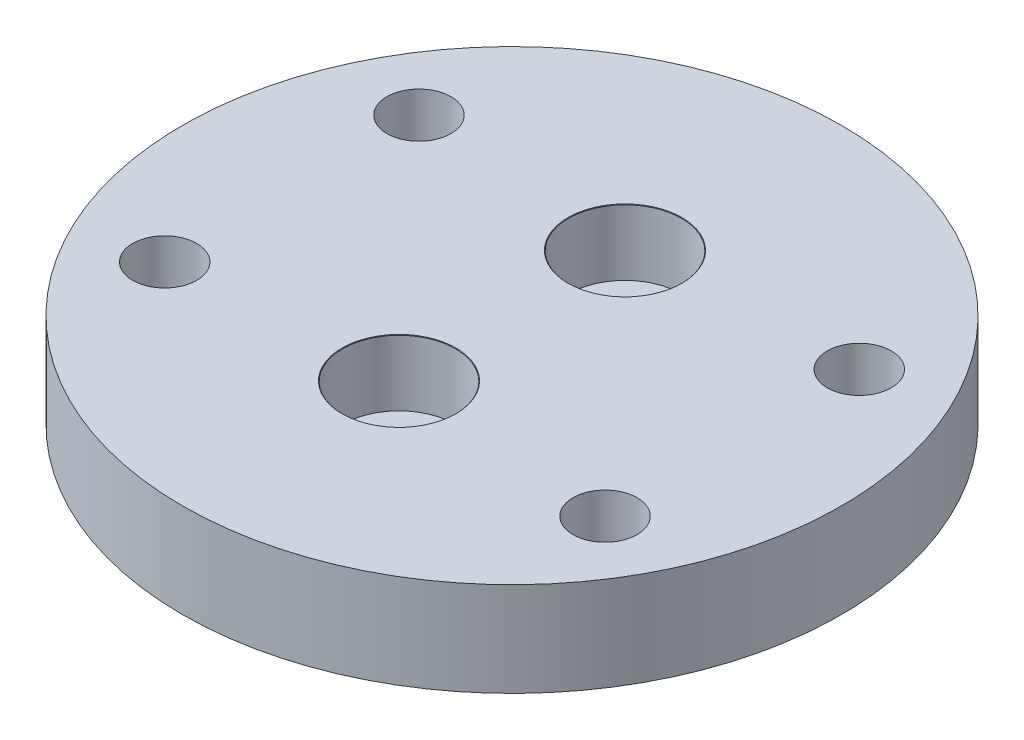
SolidWorks part; units mm, degrees
ref_plane "前视基准面" through (0, 0, 0) normal (0, 0, 1) x (1, 0, 0)
ref_plane "上视基准面" through (0, 0, 0) normal (0, 1, 0) x (1, 0, 0)
ref_plane "右视基准面" through (0, 0, 0) normal (1, 0, 0) x (0, 0, -1)
other "Configuration Table"
sketch "草图1" plane through (0, 0, 0) normal (0, 1, 0) x (1, 0, 0)
  circle A0 centre (0, 0) radius 17.5
  dimension "D1" = 35
extrude "凸台-拉伸1" add sketch "草图1" along normal blind 5
sketch "草图4" plane through (0, 0, 0) normal (0, -1, 0) x (-1, 0, 0)
  line L0 (0, 0) -> (11.6913, 6.75) construction
  circle A0 centre (0, 0) radius 13.5 construction
  point P5 (11.6913, 6.75)
  point P15 (11.6913, 6.75)
  dimension "D1" = 27
hole_wizard "M3 间隙孔1" positions "草图4" profile "草图3" hole size "M3" standard "GB" end condition up to next
sketch "草图3" plane through (-11.6913, 0, -6.75) normal (1, 0, 0) x (0, 0, -1)
  line L0 (0, 0) -> (0, 5)
  line L1 (0, 5) -> (1.7, 5)
  line L2 (1.7, 5) -> (1.7, 0.025)
  line L3 (1.7, 0.025) -> (1.725, 0)
  line L5 (1.725, 0) -> (0, 0)
  line L6 (-1.7, 0.025) -> (-1.725, 0) construction
  line L11 (0, -6.35) -> (0, 107.95) construction
  dimension "通孔孔直径" = 3.4
  dimension "通孔孔深度" = 5
  dimension "近端锥形沉头孔直径" = 3.45
  dimension "近端锥形沉头孔角度" = 90
ref_axis "基准轴1" through (0, 0, 0) along (0, -1, 0)
pattern_circular "阵列(圆周)1" count 6 over 360 about axis through (0, 0, 0) along (0, -1, 0) skipping 1, 4 of "M3 间隙孔1"
sketch "草图7" plane through (0, 5, 0) normal (0, 1, 0) x (1, 0, 0)
  line L0 (-9.4689, 0) -> (8.3011, 0) construction
  point P0 (0, 6)
  point P2 (0, -6)
  dimension "D1" = 12
hole_wizard "M3 开槽圆柱头螺钉的柱形沉头孔1" positions "草图7" profile "草图6" counterbore size "M3" standard "GB" end condition up to next
sketch "草图6" plane through (0, 5, -6) normal (1, 0, 0) x (0, 0, 1)
  line L0 (0, 0) -> (0, 5)
  line L1 (0, 5) -> (1.7, 5)
  line L3 (1.7, 5) -> (1.7, 3.5)
  line L4 (3, 3.5) -> (1.7, 3.5)
  line L5 (3, 3.5) -> (3, 0.025)
  line L6 (3, 0.025) -> (3.025, 0)
  line L7 (3.025, 0) -> (0, 0)
  line L8 (-3, 0.025) -> (-3.025, 0) construction
  line L11 (0, -6.35) -> (0, 107.95) construction
  dimension "通孔孔直径" = 3.4
  dimension "通孔孔深度" = 5
  dimension "柱形沉头孔直径" = 6
  dimension "柱形沉头孔深度" = 3.5
  dimension "近端锥形沉头孔直径" = 6.05
  dimension "近端锥形沉头孔角度" = 90
